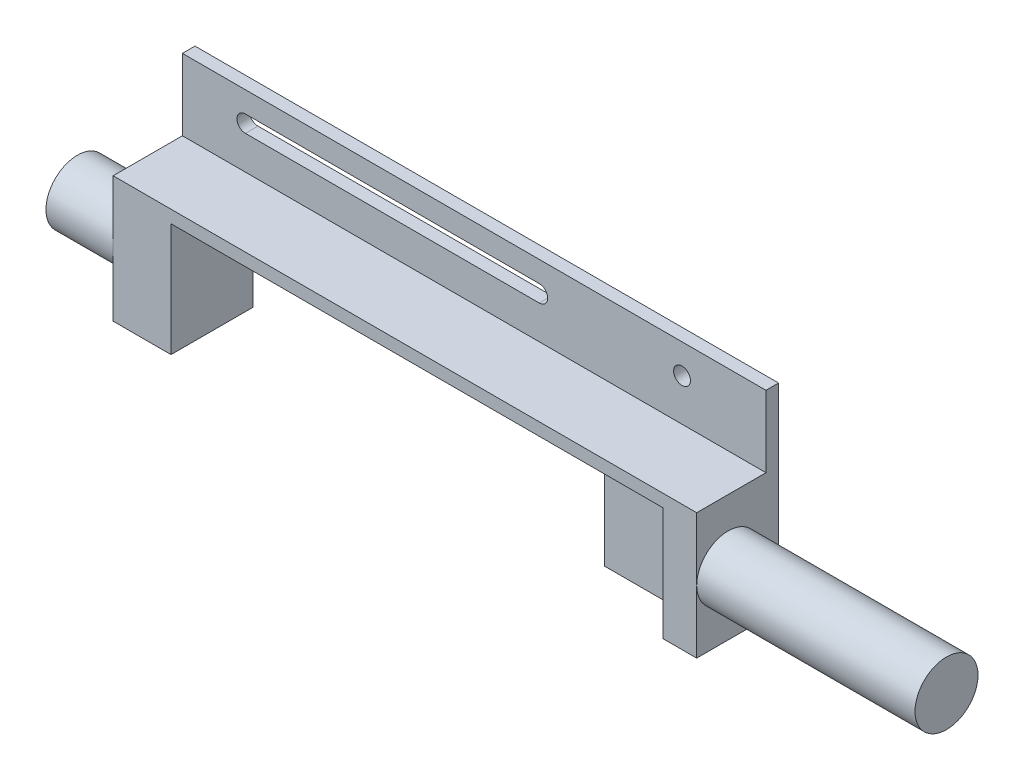
SolidWorks part; units mm, degrees
ref_plane "Front Plane" through (0, 0, 0) normal (0, 0, 1) x (1, 0, 0)
ref_plane "Top Plane" through (0, 0, 0) normal (0, 1, 0) x (1, 0, 0)
ref_plane "Right Plane" through (0, 0, 0) normal (1, 0, 0) x (0, 0, -1)
sketch "Sketch2" plane through (0, 0, 0) normal (1, 0, 0) x (0, 0, -1)
  line L0 (-6.75, 30) -> (6.75, 30)
  line L2 (-9.75, 0) -> (9.75, 0)
  line L3 (9.75, 51.1347) -> (9.75, 0)
  line L5 (-9.75, 60) -> (-6.75, 60)
  line L6 (-6.75, 30) -> (-6.75, 60)
  line L7 (9.75, 51.1347) -> (9.75, 60)
  line L8 (9.75, 60) -> (6.75, 60)
  line L9 (6.75, 30) -> (6.75, 60)
  line L10 (-9.75, 60) -> (-9.75, 0)
  point P4 (0, 0)
  dimension "D1" = 13.5
  dimension "D2" = 3
  dimension "D3" = 3
  dimension "D4" = 30
  dimension "D5" = 30
  dimension "D6" = 30
extrude "Boss-Extrude1" add sketch "Sketch2" along normal blind 139
sketch "Sketch3" plane through (0, 0, -9.75) normal (0, 0, -1) x (-1, 0, 0)
  line L0 (-85, 40) -> (-15, 40) construction
  line L1 (-85, 42) -> (-15, 42)
  line L2 (-85, 38) -> (-15, 38)
  line L3 (-139, 0) -> (-139, 60) construction
  line L4 (-139, 60) -> (0, 60) construction
  line L5 (0, 0) -> (0, 60) construction
  circle A0 centre (-119, 40) radius 2
  arc A1 (-85, 42) -> (-85, 38) centre (-85, 40) ccw
  arc A2 (-15, 38) -> (-15, 42) centre (-15, 40) ccw
  point P2 (-50, 40)
  dimension "D1" = 4
  dimension "D2" = 4
  dimension "D3" = 70
  dimension "D4" = 20
  dimension "D5" = 20
  dimension "D6" = 15
extrude "Cut-Extrude1" cut sketch "Sketch3" against normal through all
sketch "Sketch5" plane through (0, 0, -9.75) normal (0, 0, -1) x (-1, 0, 0)
  line L0 (-139, 0) -> (-139, 60) construction
  line L7 (-139, 0) -> (-109, 0)
  line L8 (-139, 0) -> (-139, 60)
  line L9 (-139, 60) -> (-109, 60)
  line L10 (-109, 0) -> (-109, 60)
  line L11 (-139, 60) -> (0, 60) construction
  dimension "D1" = 30
  dimension "D2" = 60
extrude "Boss-Extrude2" add sketch "Sketch5" along normal blind 13.7
sketch "Sketch6" plane through (0, 0, -23.45) normal (0, 0, -1) x (-1, 0, 0)
  line L0 (-139, 60) -> (-139, 0) construction
  line L1 (-139, 50.9) -> (-111.6177, 50.9)
  line L2 (-139, 50.9) -> (-139, 46.65)
  line L3 (-139, 46.65) -> (-111.6177, 46.65)
  line L4 (-111.6177, 50.9) -> (-111.6177, 46.65)
  line L5 (-111.2177, 50.9) -> (-111.2177, 49.3128) construction
  line L6 (-111.2177, 46.25) -> (-111.2177, 53.3831)
  line L7 (-126.9011, 23.5) -> (-139, 23.5) construction
  line L8 (-139, 46.25) -> (-111.2177, 46.25) construction
  line L9 (-111.2177, 46.25) -> (-124.4677, 46.25) construction
  line L10 (-111.2177, 50.9) -> (-108.8677, 50.9) construction
  line L11 (-139, 18.85) -> (-111.4177, 18.85)
  line L12 (-139, 18.85) -> (-139, 23.1)
  line L13 (-139, 23.1) -> (-111.4177, 23.1)
  line L14 (-111.4177, 18.85) -> (-111.4177, 23.1)
  line L15 (-124.4677, 23.5) -> (-111.2177, 23.5) construction
  line L16 (-111.2177, 14.5051) -> (-111.2177, 25.8744) construction
  line L17 (-111.2177, 22.175) -> (-111.2177, 20.4372) construction
  line L18 (-111.2177, 18.85) -> (-108.8677, 18.85) construction
  line M11 (-139, 60) -> (-139, 0)
  dimension "D1" = 0.4
  dimension "D2" = 0.4
  dimension "D3" = 0.4
  dimension "D4" = 0.4
extrude "Boss-Extrude3" add sketch "Sketch6" along normal blind 10 contours L11 L14 L13 M11 | L4 L1 L3 M11 region at (125.2089, 20.975, -23.45) region at (125.3089, 48.775, -23.45)
sketch "Sketch7" plane through (111.6177, 0, 0) normal (-1, 0, 0) x (0, 0, 1)
  line L1 (-33.45, 50.9) -> (-33.45, 46.65) construction
  line L2 (-33.45, 50.9) -> (-23.45, 50.9) construction
  line L3 (-33.45, 18.85) -> (-23.45, 18.85) construction
  circle A0 centre (-30.95, 48.78) radius 1
  circle A1 centre (-30.95, 20.97) radius 1
  dimension "D2" = 2
  dimension "D1" = 2.5
  dimension "D3" = 2.12
  dimension "D4" = 2.12
extrude "Cut-Extrude3" cut sketch "Sketch7" against normal through all both and the other way through all
sketch "Sketch4" plane through (139, 0, 0) normal (1, 0, 0) x (0, 0, -1)
  line L1 (-9.75, 60) -> (-9.75, 0) construction
  line L2 (-9.75, 0) -> (23.45, 0) construction
  circle A0 centre (-2.25, 15) radius 7.5
  dimension "D1" = 15
  dimension "D3" = 15
extrude "Boss-Extrude4" add sketch "Sketch4" along normal blind 52
extrude "Boss-Extrude5" add sketch "Sketch4<2>" against normal blind 155
sketch "Sketch4<2>" plane through (139, 0, 0) normal (1, 0, 0) x (0, 0, -1) same geometry as "Sketch4"
sketch "Sketch8" plane through (0, 0, 0) normal (0, -1, 0) x (1, 0, 0)
  line L0 (139, 9.75) -> (139, -23.45) construction
  line L1 (109, -23.45) -> (139, -23.45)
  line L2 (109, -23.45) -> (109, -9.75)
  line L3 (109, -9.75) -> (139, -9.75)
  line L4 (139, -23.45) -> (139, -9.75)
  point P7 (109, -9.75)
extrude "Cut-Extrude4" cut sketch "Sketch8" against normal up to surface (18.85 mm away) up to face at (125.2089, 18.85, -28.45)
sketch "Sketch9" plane through (0, 0, -9.75) normal (0, 0, -1) x (-1, 0, 0)
  line L0 (-139, 0) -> (0, 0) construction
  line L1 (-109, 0) -> (-13.793, 0)
  line L2 (-109, 0) -> (-109, 27)
  line L3 (-109, 27) -> (-13.793, 27)
  line L4 (-13.793, 0) -> (-13.793, 27)
  line L5 (-109, 18.85) -> (-109, 60) construction
  line L6 (-139, 30) -> (0, 30) construction
  point P6 (-102.0387, 0)
  point P7 (-109, 22.4697)
  point P10 (-13.793, 27.8315)
  dimension "D1" = 3
extrude "Cut-Extrude5" cut sketch "Sketch9" against normal through all
sketch "Sketch10" plane through (0, 0, 9.75) normal (0, 0, 1) x (1, 0, 0)
  line L0 (139, 60) -> (139, 15) construction
  line L1 (0, 60) -> (139, 60)
  line L2 (0, 60) -> (0, 30)
  line L3 (0, 30) -> (139, 30)
  line L4 (139, 60) -> (139, 30)
  point P7 (139, 29.7415)
extrude "Cut-Extrude6" cut sketch "Sketch10" against normal up to surface (16.5 mm away) up to face at (117, 40, -6.75)
sketch "Sketch11" plane through (0, 0, -23.45) normal (0, 0, -1) x (-1, 0, 0)
  line L0 (-109, 18.85) -> (-109, 0) construction
  line L1 (-139, 60) -> (-109, 60)
  line L2 (-139, 60) -> (-139, 14.7884)
  line L3 (-139, 14.7884) -> (-109, 14.7884)
  line L4 (-109, 60) -> (-109, 14.7884)
extrude "Cut-Extrude7" cut sketch "Sketch11" against normal up to surface (13.7 mm away) and the other way through all up to face at (50, 40, -9.75)
sketch "Sketch12" plane through (0, 0, -9.75) normal (0, 0, -1) x (-1, 0, 0)
  line L0 (0, 0) -> (0, 60) construction
  line L1 (-139, 60) -> (0, 60)
  line L2 (-139, 60) -> (-139, 47)
  line L3 (-139, 47) -> (0, 47)
  line L4 (0, 60) -> (0, 47)
  line L5 (-15, 42) -> (-85, 42) construction
  dimension "D1" = 5
extrude "Cut-Extrude8" cut sketch "Sketch12" against normal through all
sketch "Sketch13" plane through (0, 0, -9.75) normal (0, 0, -1) x (-1, 0, 0)
  line L0 (-109, 27) -> (-109, 0) construction
  line L1 (-139, 0) -> (-109, 0) construction
  circle A0 centre (-126, 7) radius 2.5
  circle A1 centre (-126, 17) radius 2.5
  point P4 (-120.7327, 18.8663)
  point P5 (-121.1343, 7.5077)
  point P6 (-118.754, 20.759)
  point P9 (0, 0)
  point P12 (-118, 20.0612)
  dimension "D1" = 5
  dimension "D2" = 5
  dimension "D3" = 17
  dimension "D4" = 7
  dimension "D5" = 10
extrude "Cut-Extrude9" cut sketch "Sketch13" against normal up to next
sketch "Sketch14" plane through (0, 0, 9.75) normal (0, 0, 1) x (1, 0, 0)
  line L0 (139, 0) -> (109, 0) construction
  line L1 (131, 0) -> (109, 0)
  line L2 (131, 0) -> (131, 27)
  line L3 (131, 27) -> (109, 27)
  line L4 (109, 0) -> (109, 27)
  line L5 (139, 30) -> (139, 15) construction
  dimension "D1" = 8
extrude "Cut-Extrude10" cut sketch "Sketch14" against normal blind 8
equation "\"D3@Sketch7\"=4.24/2"
